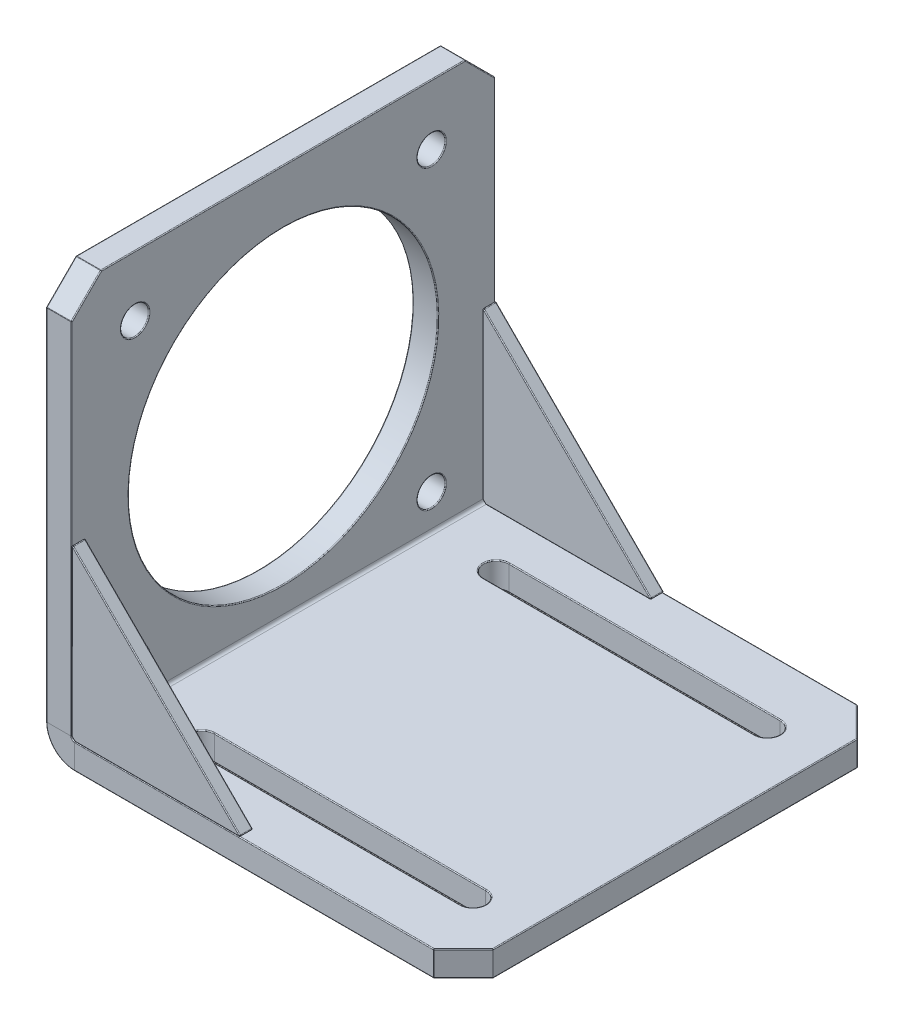
SolidWorks part; units mm, degrees
note: The reader was unsure of these and kept them because the rebuilt part matched: thickness of "Base-Flangia1", "Bordo-Flangia1", "Lamiera1", "Lamiera2", "Lamiera3", "Lamiera11"; flange length of "Bordo-Flangia1".
ref_plane "Piano frontale" through (0, 0, 0) normal (0, 0, 1) x (1, 0, 0)
ref_plane "Piano superiore" through (0, 0, 0) normal (0, 1, 0) x (1, 0, 0)
ref_plane "Piano destro" through (0, 0, 0) normal (1, 0, 0) x (0, 0, -1)
sketch "Schizzo1" plane through (0, 0, 0) normal (0, 0, 1) x (1, 0, 0)
  line L0 (0, 0) -> (98.5, 0)
  dimension "D1" = 98.5
base flange "Base-Flangia1" sketch "Schizzo1" end condition mid plane depth 100 reverse direction no thickness 6 reverse thickness direction no bend radius 0.7366
edge flange "Bordo-Flangia1" sketch "Schizzo8" flange angle 90 flange length 98.5 flange position material inside bend radius 0.7366 thickness 6 parameters "D6"=10
sketch "Schizzo8" plane through (0, 0, 0) normal (-1, 0, 0) x (0, 0, 1)
  line L0 (50, 0) -> (-50, 0) construction
  line L1 (50, 0) -> (-50, 0)
  line L2 (-50, 0) -> (-50, 92.5)
  line L3 (-50, 92.5) -> (50, 92.5)
  line L4 (50, 92.5) -> (50, 0)
  line L5 (50, -6) -> (-50, -6) construction
  point P6 (0, -6)
  dimension "D1" = 98.5
bend "PiegaturaBordo1" bend radius 0.7366 bend angle 90 parameters "D5"=1
sketch "Schizzo10" plane through (6, 0, 0) normal (1, 0, 0) x (0, 0, -1)
  line L0 (0, 92.5) -> (0, 0.7366) construction
  line L1 (-50, 92.5) -> (50, 92.5) construction
  line L2 (50, 0.7366) -> (-50, 0.7366) construction
  line L3 (50, 43.25) -> (-50, 43.25) construction
  line L4 (50, 92.5) -> (50, 0.7366) construction
  line L5 (-50, 0.7366) -> (-50, 92.5) construction
  circle A0 centre (0, 43.25) radius 36.5
  circle A1 centre (-35, 78.25) radius 3.3
  circle A2 centre (35, 78.25) radius 3.3
  circle A3 centre (-35, 8.25) radius 3.3
  circle A4 centre (35, 8.25) radius 3.3
  dimension "D1" = 73
  dimension "D2" = 49.25
  dimension "D3" = 6.6
  dimension "D4" = 70
  dimension "D5" = 70
extrude "Taglio-Estrusione1" cut sketch "Schizzo10" against normal through all normal cut yes
sketch "Schizzo12" plane through (0, 0, 0) normal (0, 1, 0) x (1, 0, 0)
  line L0 (98.5, 0) -> (0, 0) construction
  line L1 (98.5, -50) -> (98.5, 50) construction
  line L2 (98.5, 34.75) -> (0, 34.75) construction
  line L3 (98.5, -34.75) -> (0, -34.75) construction
  line L5 (21.5, 40) -> (21.5, -40) construction
  line L6 (85.5, 40) -> (85.5, -40) construction
  line L7 (85.5, 34.75) -> (21.5, 34.75) construction
  line L8 (85.5, 31.75) -> (21.5, 31.75)
  line L9 (85.5, 37.75) -> (21.5, 37.75)
  line L10 (85.5, -34.75) -> (21.5, -34.75) construction
  line L11 (85.5, -37.75) -> (21.5, -37.75)
  line L12 (85.5, -31.75) -> (21.5, -31.75)
  arc A0 (85.5, 31.75) -> (85.5, 37.75) centre (85.5, 34.75) ccw
  arc A1 (21.5, 37.75) -> (21.5, 31.75) centre (21.5, 34.75) ccw
  arc A2 (85.5, -37.75) -> (85.5, -31.75) centre (85.5, -34.75) ccw
  arc A3 (21.5, -31.75) -> (21.5, -37.75) centre (21.5, -34.75) ccw
  point P9 (21.5, 0)
  point P10 (85.5, 0)
  point P17 (53.5, 34.75)
  point P22 (53.5, -34.75)
  dimension "D5" = 13
  dimension "D3" = 6
  dimension "D2" = 64
  dimension "D4" = 34.75
  dimension "D1" = 69.5
extrude "Taglio-Estrusione3" cut sketch "Schizzo12" against normal through all normal cut yes
sketch "Schizzo15" plane through (0, 0, 0) normal (0, 0, 1) x (1, 0, 0)
  line L0 (0, 40) -> (5.1835, 40) construction
  line L1 (0, 0.7366) -> (0, 92.5) construction
  line L2 (46, -6) -> (46, 2.1352) construction
  line L3 (6.7366, -6) -> (98.5, -6) construction
  line L4 (13.7349, 0) -> (-1.1225, 0) construction
  line L5 (85.5, 0) -> (21.5, 0) construction
  line L6 (6, 40) -> (6, -3.5666) construction
  line L7 (6, 0.7366) -> (6, 92.5) construction
  line L8 (6, 40) -> (46, 0)
  line L9 (46, 0) -> (6.7366, 0)
  line L10 (6.7366, 0) -> (6, 0.7366)
  line L11 (6, 0.7366) -> (6, 40)
  dimension "D1" = 40
  dimension "D2" = 40
extrude "Estrusione-Estrusione3" add sketch "Schizzo15" against normal blind 3 from surface at 50 separate body starting at face at (3, 46.6183, 50)
mirror "Specchia5" about plane through (0, 0, 0) normal (0, 0, 1) of bodies 109
chamfer "Smusso1" distance 7 angle 45 4 edges at (98.5, -3, 50) (98.5, -3, -50) (3, 92.5, -50) (3, 92.5, 50)
fillet "Raccordo1" radius 0.2 58 edges at (98.5, 0, 0) (98.5, -6, 0) (98.5, -3, -43) (98.5, -3, 43) (95, -6, -46.5) (95, -6, 46.5) (91.5, -3, 50) (95, 0, -46.5) (95, 0, 46.5) (91.5, -3, -50) (0, 43.1183, -50) (6, 43.1183, -50) (3, 85.5, -50) (6, 92.5, 0) (49.1183, -6, -50) (6, 89, 46.5) (6, 89, -46.5) (0, 92.5, 0) (3, 92.5, 43) (3, 92.5, -43) (49.1183, 0, -50) (0, 89, 46.5) (0, 89, -46.5) (3, 85.5, 50) (49.1183, -6, 50) (49.1183, 0, 50) (1.9731, -4.0269, -50) (1.9731, -4.0269, 50) (6.2157, 0.2157, -50) (6.2157, 0.2157, 50) (6, 43.1183, 50) (0, 43.1183, 50) (0, 11.55, -35) (6, 11.55, -35) (0, 4.95, 35) (6, 4.95, 35) (0, 74.95, -35) (6, 74.95, -35) (0, 81.55, 35) (6, 81.55, 35) (0, 79.75, 0) (6, 79.75, 0) (88.5, -6, -34.75) (53.5, -6, -31.75) (18.5, -6, -34.75) (53.5, -6, -37.75) (88.5, 0, -34.75) (53.5, 0, -37.75) (18.5, 0, -34.75) (53.5, 0, -31.75) (88.5, -6, 34.75) (53.5, -6, 37.75) (18.5, -6, 34.75) (53.5, -6, 31.75) (88.5, 0, 34.75) (53.5, 0, 31.75) (18.5, 0, 34.75) (53.5, 0, 37.75)
fillet "Raccordo2" radius 0.2 10 edges at (6.3683, 0.3683, -47) (6, 20.3683, -47) (26.3683, 0, -47) (46, 0, -48.5) (26, 20, -47) (6, 40, -48.5) (26, 20, -50) (6, 20.3683, -50) (6.3683, 0.3683, -50) (26.3683, 0, -50)
fillet "Raccordo3" radius 0.2 10 edges at (6.3683, 0.3683, 50) (6, 20.3683, 50) (26.3683, 0, 50) (6, 40, 48.5) (46, 0, 48.5) (26, 20, 50) (26, 20, 47) (6, 20.3683, 47) (6.3683, 0.3683, 47) (26.3683, 0, 47)
sketch "Linee di piegatura1" [suppressed] plane through (0, 0, 0) normal (0, 1, 0) x (1, 0, 0)
sketch "Casella di contorno1" [suppressed] plane through (0, 0, 0) normal (0, 1, 0) x (1, 0, 0)
sheet metal parameters "Lamiera1" thickness 6 parameters "D1"=0.7366
flat pattern "Ripetizione piatta1" [suppressed]
sketch "Linee di piegatura2" plane through (0, 0, 0) normal (0, 1, 0) x (1, 0, 0)
sketch3d "Casella di contorno2" [suppressed]
  line L0 (0, 41.3, 0) -> (0, 0, 0) construction
  line L1 (35, 41.3, 0) -> (35, 0, 0) construction
  line L2 (0, 41.3, 0) -> (35, 41.3, 0) construction
  line L3 (0, 0, 0) -> (35, 0, 0) construction
sheet metal parameters "Lamiera2" thickness 6 parameters "D1"=0.7366, "D7"=3
flat pattern "Ripetizione piatta1"
sketch "Linee di piegatura2" plane through (0, 0, 0) normal (0, 1, 0) x (1, 0, 0)
  line L0 (1.98, -25) -> (1.98, 25) construction
  line L1 (1.98, -25) -> (1.98, 25) construction
sketch3d "Casella di contorno2" [suppressed]
  line L0 (53, 0, 0) -> (-47.04, 0, 0) construction
  line L1 (53, 50, 0) -> (-47.04, 50, 0) construction
  line L2 (53, 0, 0) -> (53, 50, 0) construction
  line L3 (-47.04, 0, 0) -> (-47.04, 50, 0) construction
bend of the flat pattern "Appiattito-<PiegaturaBordo1>1"
sheet metal parameters "Lamiera3" thickness 6 parameters "D1"=0.7366, "D7"=3
flat pattern "Ripetizione piatta1"
sketch "Linee di piegatura2" plane through (0, 0, 0) normal (0, 1, 0) x (1, 0, 0)
  line L0 (1.98, -25) -> (1.98, 25) construction
  line L1 (1.98, -25) -> (1.98, 25) construction
sketch3d "Casella di contorno2" [suppressed]
  line L0 (53, 0, 0) -> (-47.04, 0, 0) construction
  line L1 (53, 50, 0) -> (-47.04, 50, 0) construction
  line L2 (53, 0, 0) -> (53, 50, 0) construction
  line L3 (-47.04, 0, 0) -> (-47.04, 50, 0) construction
bend of the flat pattern "Appiattito-<PiegaturaBordo1>1"
sheet metal parameters "Lamiera11" thickness 6 parameters "D1"=0.7366, "D7"=3
flat pattern "Ripetizione piatta1"
sketch "Linee di piegatura2" plane through (0, 0, 0) normal (0, 1, 0) x (1, 0, 0)
  line L0 (3.8019, -49.8) -> (3.8019, 49.8) construction
  line L1 (3.8019, -49.8) -> (3.8019, 49.8) construction
sketch3d "Casella di contorno2" [suppressed]
  line L0 (-90.8962, 0, 0) -> (98.5, 0, 0) construction
  line L1 (-90.8962, 100, 0) -> (98.5, 100, 0) construction
  line L2 (-90.8962, 0, 0) -> (-90.8962, 100, 0) construction
  line L3 (98.5, 0, 0) -> (98.5, 100, 0) construction
bend of the flat pattern "Appiattito-<PiegaturaBordo1>1"
